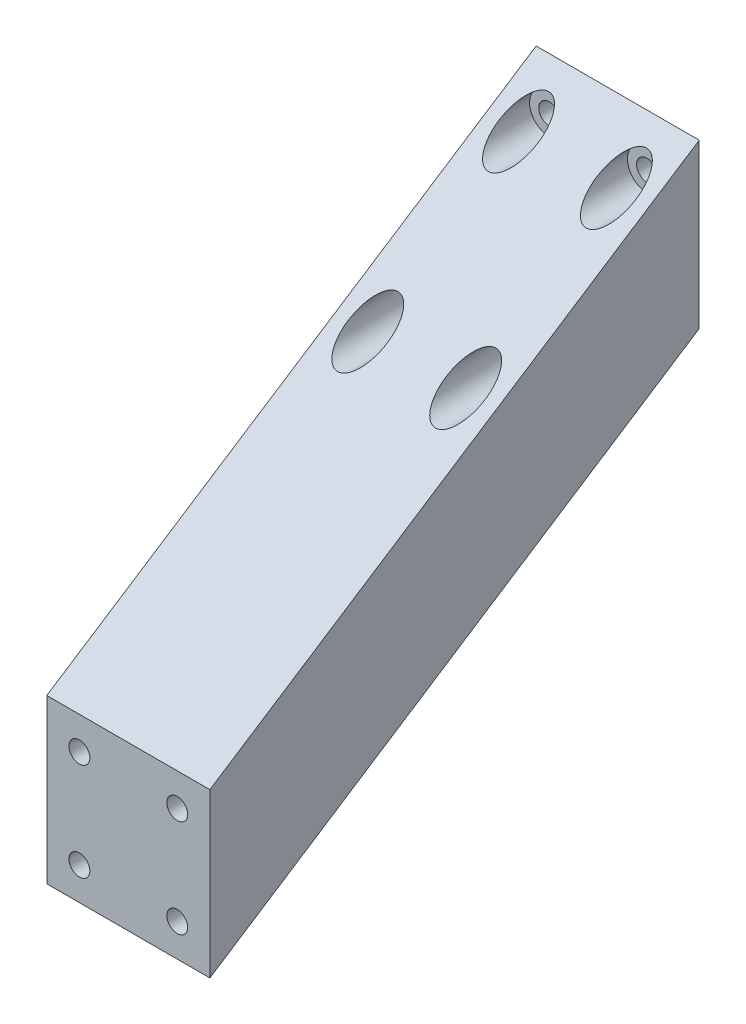
SolidWorks part; units mm, degrees
ref_plane "Front Plane" through (0, 0, 0) normal (0, 0, 1) x (1, 0, 0)
ref_plane "Top Plane" through (0, 0, 0) normal (0, 1, 0) x (1, 0, 0)
ref_plane "Right Plane" through (0, 0, 0) normal (1, 0, 0) x (0, 0, -1)
sketch "Sketch1" plane through (0, 0, 0) normal (1, 0, 0) x (0, 0, -1)
  line L0 (0, 40.3987) -> (0, -48.7056) construction
  line L1 (0, 0) -> (-75, -48.7056)
  line L2 (0, -48.7056) -> (-75, -48.7056) construction
  line L5 (0, 25) -> (0, 0)
  line L7 (-75, -48.7056) -> (-75, -23.7056)
  line L8 (-75, -23.7056) -> (0, 25)
  dimension "D1" = 33
  dimension "D2" = 75
  dimension "D4" = 25
  dimension "D5" = 25
extrude "Boss-Extrude1" add sketch "Sketch1" along normal blind 25
sketch "Sketch3" plane through (0, 0, 0) normal (0, 0, -1) x (-1, 0, 0)
  line L2 (-20, 20) -> (-20, 5) construction
  line L3 (0, 0) -> (0, 25) construction
  line L4 (-25, 25) -> (0, 25) construction
  line L5 (-25, 0) -> (-25, 25) construction
  circle A0 centre (-20, 20) radius 1.6
  circle A1 centre (-20, 20) radius 3
  circle A2 centre (-20, 5) radius 3
  circle A3 centre (-20, 5) radius 1.6
  circle A4 centre (-5, 5) radius 3
  circle A5 centre (-5, 5) radius 1.6
  circle A6 centre (-5, 20) radius 3
  circle A7 centre (-5, 20) radius 1.6
  dimension "D1" = 6
  dimension "D2" = 3.2
  dimension "D3" = 5
  dimension "D4" = 5
  dimension "D7" = 15
  dimension "D8" = 5
  dimension "D5" = 2
  dimension "D6" = 2
extrude "Cut-Extrude7" cut sketch "Sketch3" against normal up to next from offset 3 offset against normal yes
extrude "Cut-Extrude8" cut sketch "Sketch3<3>" against normal up to next contours A7 | A0 | A5 | A3 region at (20, 20, 0) region at (20, 5, 0) region at (5, 5, 0) region at (5, 20, 0)
sketch "Sketch3<3>" plane through (0, 0, 0) normal (0, 0, -1) x (-1, 0, 0) same geometry as "Sketch3"
sketch "Sketch4" plane through (0, 0, 75) normal (0, 0, 1) x (1, 0, 0)
  line L0 (5, -28.7056) -> (5, -33.9645) construction
  line L1 (25, -23.7056) -> (0, -23.7056) construction
  line L2 (0, -23.7056) -> (0, -48.7056) construction
  line L3 (5, -28.7056) -> (5, -43.7056) construction
  circle A0 centre (5, -28.7056) radius 1.6
  circle A1 centre (5, -28.7056) radius 3
  circle A8 centre (5, -43.7056) radius 1.6
  circle A9 centre (5, -43.7056) radius 3
  circle A10 centre (20, -43.7056) radius 1.6
  circle A11 centre (20, -43.7056) radius 3
  circle A12 centre (20, -28.7056) radius 1.6
  circle A13 centre (20, -28.7056) radius 3
  dimension "D1" = 6
  dimension "D2" = 3.2
  dimension "D3" = 5
  dimension "D4" = 5
  dimension "D7" = 15
  dimension "D5" = 2
  dimension "D6" = 2
extrude "Cut-Extrude9" cut sketch "Sketch4" against normal up to next from offset 3 offset against normal yes
extrude "Cut-Extrude10" cut sketch "Sketch4<2>" against normal up to next contours A0 | A12 | A10 | A8 region at (5, -28.7056, 75) region at (5, -43.7056, 75) region at (20, -43.7056, 75) region at (20, -28.7056, 75)
sketch "Sketch4<2>" plane through (0, 0, 75) normal (0, 0, 1) x (1, 0, 0) same geometry as "Sketch4"
